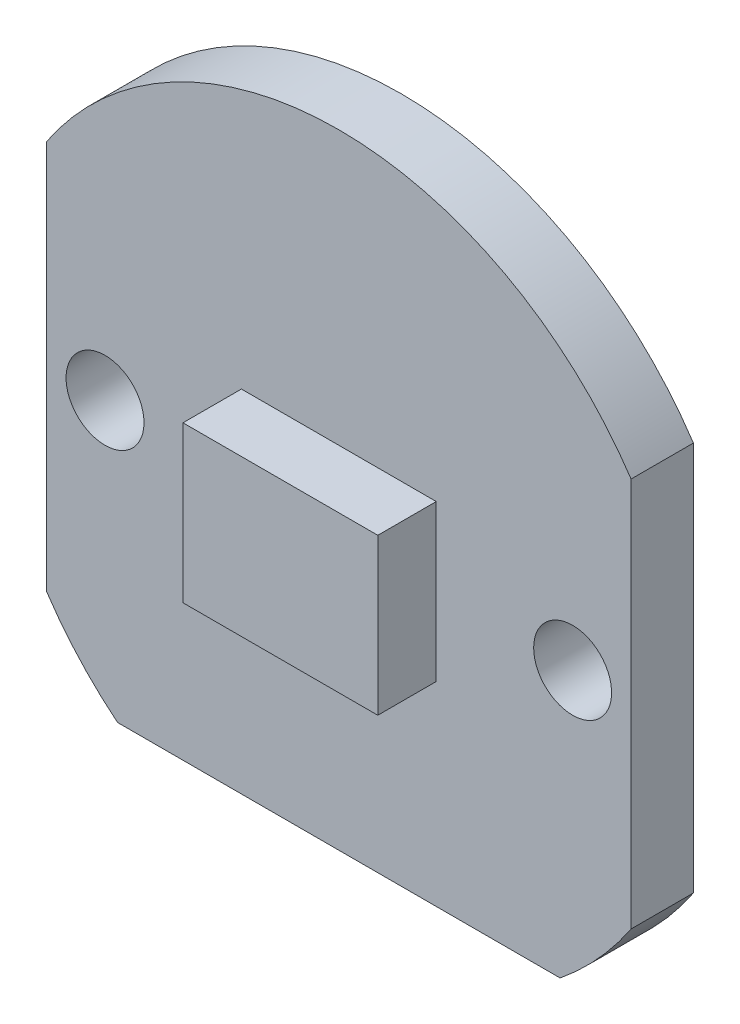
SolidWorks part; units mm, degrees
ref_plane "Front Plane" through (0, 0, 0) normal (0, 0, 1) x (1, 0, 0)
ref_plane "Top Plane" through (0, 0, 0) normal (0, 1, 0) x (1, 0, 0)
ref_plane "Right Plane" through (0, 0, 0) normal (1, 0, 0) x (0, 0, -1)
sketch "Sketch1" plane through (0, 0, 0) normal (0, 0, 1) x (1, 0, 0)
  line L0 (-5.6789, -7) -> (5.6789, -7)
  line L1 (-7.5, -5) -> (7.5, -5) construction
  line L2 (-7.5, -5) -> (-7.5, 5)
  line L3 (-7.5, 5) -> (7.5, 5) construction
  line L4 (7.5, -5) -> (7.5, 5)
  line L5 (-7.5, -5) -> (7.5, 5) construction
  line L6 (-7.5, 5) -> (7.5, -5) construction
  line L7 (-7.5, 0) -> (7.5, 0) construction
  line L8 (0, 5) -> (0, -5) construction
  circle A0 centre (0, 0) radius 9.0139 construction
  circle A1 centre (0, 0) radius 9.0139 construction
  arc A2 (-7.5, 5) -> (7.5, 5) centre (0, 0) cw
  arc A3 (-7.5, -5) -> (-5.6789, -7) centre (0, 0) ccw
  arc A4 (5.6789, -7) -> (7.5, -5) centre (0, 0) ccw
  circle A5 centre (-6, 0) radius 1
  circle A6 centre (6, 0) radius 1
  dimension "D1" = 15
  dimension "D4" = 2
  dimension "D2" = 10
  dimension "D3" = 2
  dimension "D5" = 1.5
extrude "Boss-Extrude1" add sketch "Sketch1" along normal blind 1.6 contours A3 L0 A4 L4 A2 L2 | A5 | A6
sketch "Sketch2" plane through (0, 0, 1.6) normal (0, 0, 1) x (1, 0, 0)
  line L1 (-2.5, -2) -> (2.5, -2)
  line L2 (-2.5, -2) -> (-2.5, 2)
  line L3 (-2.5, 2) -> (2.5, 2)
  line L4 (2.5, -2) -> (2.5, 2)
  line L5 (-2.5, -2) -> (2.5, 2) construction
  line L6 (-2.5, 2) -> (2.5, -2) construction
  point P0 (0, 0)
  dimension "D1" = 4
  dimension "D2" = 5
extrude "Boss-Extrude2" add sketch "Sketch2" along normal blind 1.5
ref_plane "Plane1" through (0, 0, 0) normal (0, 1, 0) x (1, 0, 0)
ref_plane "Plane2" through (0, 0, 0) normal (-1, 0, 0) x (0, 0, 1)
ref_axis "Axis1" through (0, 0, 1.525) along (0, 0, 1)
